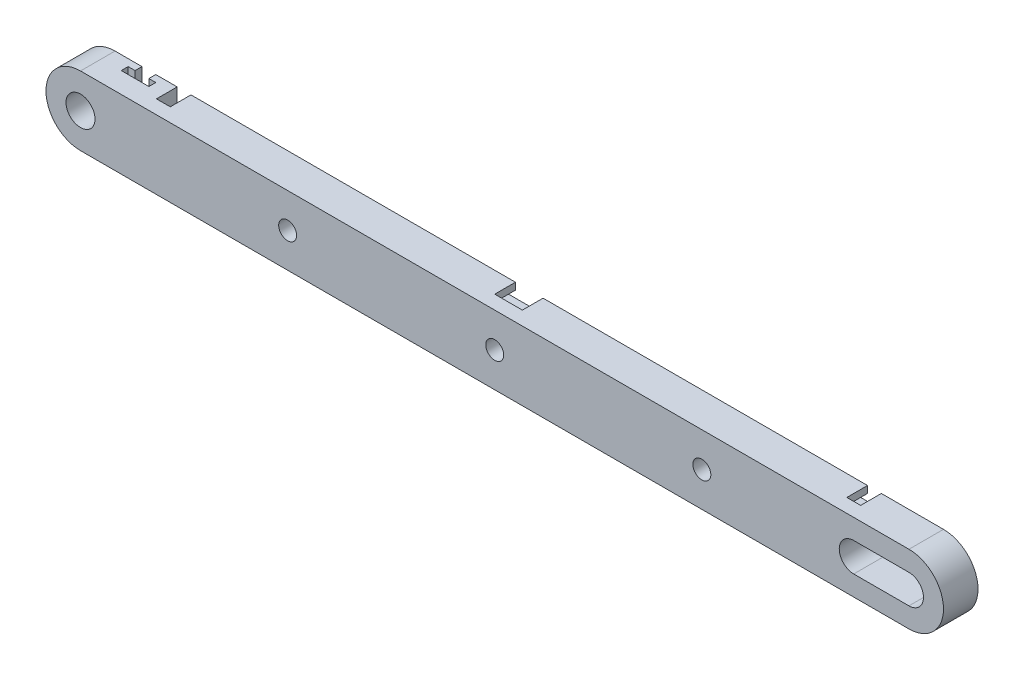
SolidWorks part; units mm, degrees
ref_plane "Plan de face" through (0, 0, 0) normal (0, 0, 1) x (1, 0, 0)
ref_plane "Plan de dessus" through (0, 0, 0) normal (0, 1, 0) x (1, 0, 0)
ref_plane "Plan de droite" through (0, 0, 0) normal (1, 0, 0) x (0, 0, -1)
sketch "Esquisse1" plane through (0, 0, 0) normal (0, 0, 1) x (1, 0, 0)
  line L0 (600, 0) -> (0, 0) construction
  line L1 (600, -25) -> (0, -25)
  line L2 (600, 25) -> (0, 25)
  line L3 (560, 0) -> (600, 0) construction
  line L4 (560, 10.5) -> (600, 10.5)
  line L5 (560, -10.5) -> (600, -10.5)
  line L6 (300, 66.3558) -> (300, -50.0797) construction
  line L7 (290, 25) -> (290, 20)
  line L8 (290, 20) -> (282.5, 20)
  line L9 (282.5, 20) -> (282.5, 15)
  line L10 (282.5, 15) -> (317.5, 15)
  line L11 (317.5, 15) -> (317.5, 20)
  line L12 (317.5, 20) -> (310, 20)
  line L13 (310, 20) -> (310, 25)
  line L15 (545, 25) -> (545, 20)
  line L16 (545, 20) -> (537.5, 20)
  line L17 (537.5, 20) -> (537.5, 15)
  line L18 (537.5, 15) -> (555, 15)
  line L21 (55, 20) -> (55, 25)
  line L22 (45, 25) -> (45, 15)
  line L23 (555, 25) -> (555, 15)
  line L25 (45, 15) -> (62.5, 15)
  line L26 (62.5, 20) -> (55, 20)
  line L27 (62.5, 15) -> (62.5, 20)
  line L28 (35, 25) -> (35, 20) [skipped]
  line L30 (35, 20) -> (27.5, 20) [skipped]
  line L31 (27.5, 20) -> (27.5, 15) [skipped]
  line L32 (572.5, 20) -> (565, 20) [skipped]
  line L33 (572.5, 15) -> (572.5, 20) [skipped]
  line L34 (565, 20) -> (565, 25) [skipped]
  arc A0 (600, -25) -> (600, 25) centre (600, 0) ccw
  arc A1 (0, 25) -> (0, -25) centre (0, 0) ccw
  circle A3 centre (0, 0) radius 10.5
  arc A4 (560, 10.5) -> (560, -10.5) centre (560, 0) ccw
  arc A5 (600, -10.5) -> (600, 10.5) centre (600, 0) ccw
  circle A6 centre (300, 0) radius 6.5
  circle A7 centre (300, 0) radius 10
  circle A8 centre (450, 0) radius 10
  circle A9 centre (450, 0) radius 6.5
  circle A10 centre (150, 0) radius 6.5
  circle A11 centre (150, 0) radius 10
  point P2 (300, 0)
  point P11 (580, 0)
  point P20 (310, 22.5)
  point P36 (555, 20)
  dimension "D2" = 25
  dimension "D3" = 40
  dimension "D4" = 0
  dimension "D1" = 10.5
  dimension "D8" = 21
  dimension "D9" = 20
  dimension "D6" = 560
  dimension "D20" = 20
  dimension "D21" = 13
  dimension "D25" = 150
  dimension "D5" = 0
  dimension "D7" = 0
  dimension "D10" = 10
  dimension "D11" = 35
  dimension "D12" = 5
  dimension "D13" = 10
  dimension "D15" = 2
  dimension "D16" = 220
  dimension "D17" = 220
  dimension "D18" = 10
  dimension "D19" = 10
  dimension "D24" = 150
  dimension "D14" = 2
  dimension "D22" = 2
  dimension "D23" = 2
extrude "Boss.-Extru.1" add sketch "Esquisse1" along normal blind 25 contours L2 A1 L1 A0 | A4 L5 A5 L4 | A3
sketch "Esquisse2" plane through (0, 25, 0) normal (0, 1, 0) x (1, 0, 0)
  line L6 (510, 0) -> (500, 0)
  line L11 (500, 0) -> (500, -5)
  line L16 (600, 0) -> (0, 0) construction
  line L21 (500, -5) -> (495, -5)
  line L22 (495, -5) -> (495, -10)
  line L23 (495, -10) -> (515, -10)
  line L26 (515, -5) -> (515, -10)
  line L27 (510, -5) -> (515, -5)
  line L28 (510, 0) -> (510, -5)
  line L29 (600, -25) -> (600, 0) construction
  dimension "D1" = 10
  dimension "D2" = 85
  dimension "D3" = 20
  dimension "D4" = 5
  dimension "D6" = 5
  dimension "D7" = 10
extrude "Enlèv. mat.-Extru.1" cut sketch "Esquisse2" against normal blind 35 from offset 15 contours L28 L27 L26 L23 L22 L21 L11 L6 offset against normal yes
sketch "Esquisse3" plane through (0, -25, 0) normal (0, -1, 0) x (1, 0, 0)
  line L0 (19.5, 0) -> (19.5, 5)
  line L1 (0, 0) -> (500, 0) construction
  line L2 (19.5, 5) -> (14.5, 5)
  line L3 (14.5, 5) -> (14.5, 10)
  line L4 (14.5, 10) -> (34.5, 10)
  line L5 (34.5, 10) -> (34.5, 5)
  line L6 (34.5, 5) -> (29.5, 5)
  line L7 (29.5, 5) -> (29.5, 0)
  line L8 (29.5, 0) -> (19.5, 0)
  line L9 (0, 25) -> (0, 0) construction
  dimension "D1" = 20
  dimension "D2" = 10
  dimension "D3" = 5
  dimension "D4" = 10
  dimension "D5" = 19.5
extrude "Enlèv. mat.-Extru.2" cut sketch "Esquisse3" against normal blind 50
extrude "Enlèv. mat.-Extru.3" cut sketch "Esquisse1<3>" along normal blind 15 contours L25 L27 L26 L21 L2 | L12 L13 L2 L7 L8 L9 L10 L11 | L18 L2 L15 L16 L17 region at (547.6136, 19.3182, 0) region at (52.3864, 19.3182, 0) region at (300, 19.3182, 0)
sketch "Esquisse1<3>" plane through (0, 0, 0) normal (0, 0, 1) x (1, 0, 0) same geometry as "Esquisse1"
extrude "Enlèv. mat.-Extru.4" cut sketch "Esquisse1<4>" against normal through all both and the other way through all contours A6 | A9 | A10
sketch "Esquisse1<4>" plane through (0, 0, 0) normal (0, 0, 1) x (1, 0, 0) same geometry as "Esquisse1"
extrude "Enlèv. mat.-Extru.5" cut sketch "Esquisse1<5>" along normal blind 12 contours A7 | A11 | A8
sketch "Esquisse1<5>" plane through (0, 0, 0) normal (0, 0, 1) x (1, 0, 0) same geometry as "Esquisse1"
